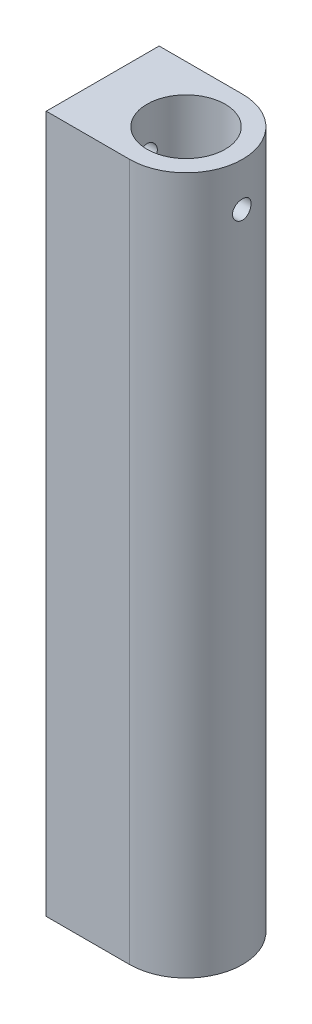
SolidWorks part; units mm, degrees
ref_plane "Front Plane" through (0, 0, 0) normal (0, 0, 1) x (1, 0, 0)
ref_plane "Top Plane" through (0, 0, 0) normal (0, 1, 0) x (1, 0, 0)
ref_plane "Right Plane" through (0, 0, 0) normal (1, 0, 0) x (0, 0, -1)
sketch "Sketch1" plane through (0, 0, 0) normal (0, 1, 0) x (1, 0, 0)
  line L0 (0, 8.255) -> (-12.192, 8.255)
  line L1 (-12.192, 8.255) -> (-12.192, -8.255)
  line L2 (-12.192, -8.255) -> (0, -8.255)
  circle A0 centre (0, 0) radius 5.715
  arc A1 (0, -8.255) -> (0, 8.255) centre (0, 0) ccw
  dimension "D1" = 11.43
  dimension "D2" = 16.51
  dimension "D3" = 12.192
extrude "Boss-Extrude1" add sketch "Sketch1" along normal blind 101.981
sketch "Sketch4" plane through (0, 0, 0) normal (0, -1, 0) x (1, 0, 0)
  circle A0 centre (0, 0) radius 5.715
  circle A1 centre (0, 0) radius 5.08
  circle A2 centre (0, 0) radius 5.715 construction
  dimension "D1" = 10.16
extrude "Boss-Extrude2" add sketch "Sketch4" against normal blind 3.81
hole_wizard "#6-32 Tapped Hole1" positions "Sketch5" profile "Sketch6" tap size "#6-32" standard "ANSI Inch" end condition through all
sketch "Sketch5" plane through (-12.192, 0, 0) normal (-1, 0, 0) x (0, 0, 1)
  line L0 (-8.255, 101.981) -> (8.255, 101.981) construction
  line L1 (8.255, 101.981) -> (8.255, 0) construction
  line L2 (0, 101.981) -> (0, 95.631) construction
  point P0 (0, 95.631)
  point P11 (0, 0)
  dimension "D1" = 6.35
  dimension "D2" = 8.255
sketch "Sketch6" plane through (-12.192, 95.631, 0) normal (0, 1, 0) x (0, 0, 1)
  line L0 (0, 0) -> (0, 20.447)
  line L1 (0, 20.447) -> (1.3525, 20.447)
  line L2 (1.3525, 20.447) -> (1.3525, 0)
  line L5 (1.3525, 0) -> (0, 0)
  line L11 (0, -6.35) -> (0, 107.95) construction
  dimension "Thru Tap Drill Dia." = 2.7051
  dimension "Thru Tap Drill Depth" = 20.447
cosmetic thread "Hole Thread1" parameters "D2"=3.5052
